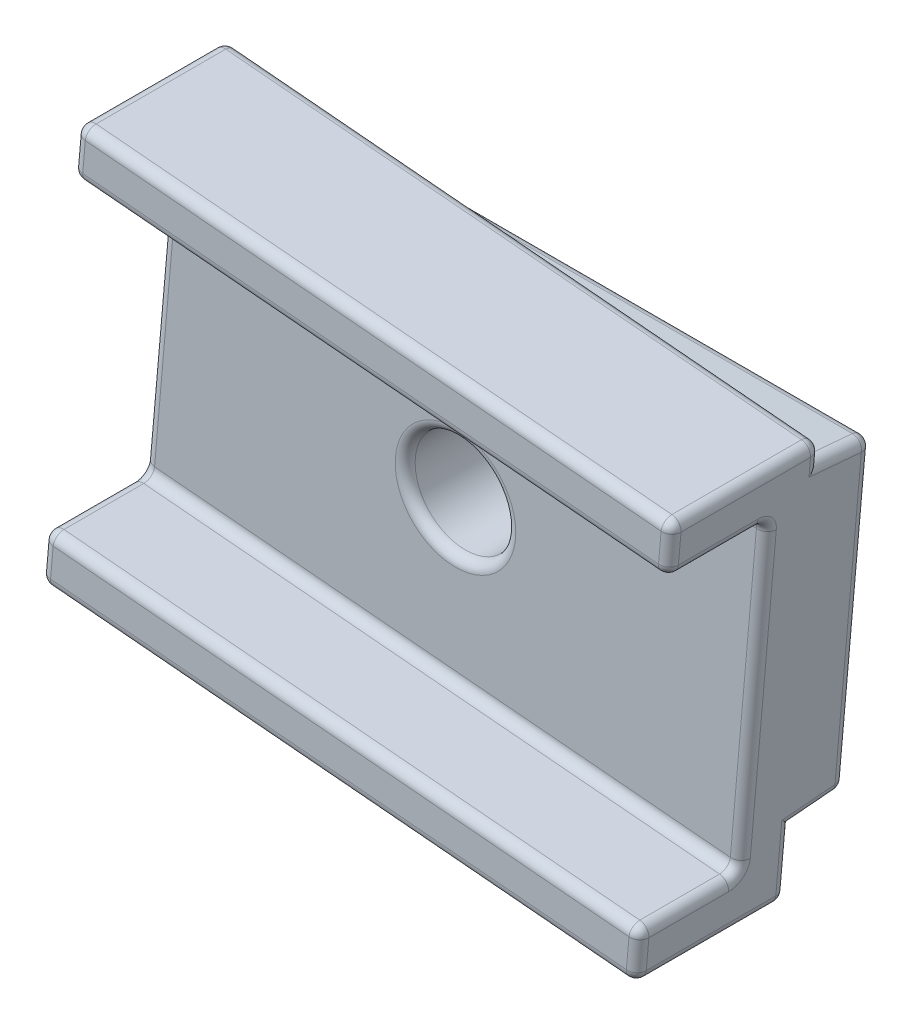
SolidWorks part; units mm, degrees
ref_plane "Front Plane" through (0, 0, 0) normal (0, 0, 1) x (1, 0, 0)
ref_plane "Top Plane" through (0, 0, 0) normal (0, 1, 0) x (1, 0, 0)
ref_plane "Right Plane" through (0, 0, 0) normal (1, 0, 0) x (0, 0, -1)
sketch "Sketch1" plane through (0, 0, 0) normal (0, 0, 1) x (1, 0, 0)
  line L1 (0, 0) -> (60, 0)
  line L2 (0, 0) -> (0, 32)
  line L3 (0, 32) -> (60, 32)
  line L4 (60, 0) -> (60, 32)
  dimension "D1" = 32
  dimension "D2" = 60
extrude "Boss-Extrude1" add sketch "Sketch1" along normal blind 5.3
sketch "Sketch3" plane through (0, 0, 0) normal (-1, 0, 0) x (0, 0, 1)
  line L0 (5.3, 32.5) -> (5.3, -0.5)
  line L1 (5.3, 32) -> (5.3, 0) construction
  line L2 (5.3, -0.5) -> (0, 0)
  line L3 (5.3, 32.5) -> (0, 32)
  line L8 (0, 32) -> (0, 0)
  line L9 (0, 0) -> (5.3, 0)
  line L10 (5.3, 0) -> (5.3, 32)
  line L11 (5.3, 32) -> (0, 32)
  line L13 (0, 0) -> (5.3, 0)
  line L14 (5.3, 0) -> (5.3, 32)
  line L15 (5.3, 32) -> (0, 32)
  point P4 (5.3, 16)
  line M7 (0, 0) -> (5.3, 0)
  line M9 (5.3, 32) -> (0, 32)
  dimension "D1" = 33
  dimension "D2" = 0
extrude "Boss-Extrude2" add sketch "Sketch3" against normal up to surface (60 mm away) contours L0 L3 M9 | L2 L0 M7 region at (0, 32.1667, 3.5333) region at (0, -0.1667, 3.5333) up to face at (60, 16, 2.65)
sketch "Sketch4" plane through (0, 0, 5.3) normal (0, 0, 1) x (1, 0, 0)
  line L0 (30, 32.5) -> (30, 16) construction
  line L1 (60, 32.5) -> (0, 32.5) construction
  line L2 (30, 16) -> (0, 16) construction
  line L3 (0, 32.5) -> (0, -0.5) construction
  line L4 (31.3945, 31.9391) -> (28.6055, 0.0609) construction
  line L5 (62.3171, -2.8885) -> (-5.1061, 3.0103)
  line L6 (62.3171, -2.8885) -> (65.1061, 28.9897)
  line L7 (65.1061, 28.9897) -> (-2.3171, 34.8885)
  line L8 (-5.1061, 3.0103) -> (-2.3171, 34.8885)
  line L9 (62.3171, -2.8885) -> (-2.3171, 34.8885) construction
  line L10 (65.1061, 28.9897) -> (-5.1061, 3.0103) construction
  line L11 (30, 16) -> (-3.7116, 18.9494) construction
  line L12 (1.5087, 34.5538) -> (-1.2803, 2.6756)
  line L13 (61.2803, 29.3244) -> (58.4913, -2.5538)
  line L14 (1.5087, 34.5538) -> (1.9444, 39.5348)
  line L15 (1.9444, 39.5348) -> (62.9835, 34.1945)
  line L16 (61.2803, 29.3244) -> (61.7161, 34.3054)
  line L17 (-1.2803, 2.6756) -> (-1.7161, -2.3054)
  line L18 (-1.7161, -2.3054) -> (58.0556, -7.5348)
  line L19 (58.4913, -2.5538) -> (58.0556, -7.5348)
  circle A0 centre (30, 16) radius 5.05
  line M3 (0, 32.5) -> (0, -0.5)
  line M4 (0, -0.5) -> (60, -0.5)
  line M5 (60, -0.5) -> (60, 32.5)
  line M6 (60, 32.5) -> (0, 32.5)
  dimension "D9" = 10.1
  dimension "D1" = 32
  dimension "D2" = 90
  dimension "D3" = 90
  dimension "D4" = 90
  dimension "D5" = 30
  dimension "D6" = 30
  dimension "D7" = 5
  dimension "D8" = 5
extrude "Boss-Extrude3" add sketch "Sketch4" along normal blind 5 contours L7 L12 M6 | L13 L7 L12 L5 A0 M5 M6 M3 M4 | L5 M4 M3 | L19 L5 L17 L18 M4 M3 | L13 L5 M4 | L13 L7 M5 | L7 M5 M6 | L7 L16 L15 L14 M6 M5 | L12 L5 M3 region at (32.0268, -3.072, 5.3) region at (50.7263, -1.1846, 5.3) region at (11.6722, 0.5212, 5.3) region at (17.5679, 1.7139, 5.3) region at (60.4268, 24.4837, 5.3) region at (27.9732, 35.072, 5.3) region at (-0.4268, 7.5163, 5.3) region at (48.3278, 31.4788, 5.3) region at (9.2737, 33.1846, 5.3)
extrude "Boss-Extrude4" add sketch "Sketch4<3>" along normal blind 15 contours L7 L16 L15 L14 M6 M5 | L7 M5 M6 | L19 L5 L17 L18 M4 M3 | L5 M4 M3 region at (32.0268, -3.072, 5.3) region at (11.6722, 0.5212, 5.3) region at (27.9732, 35.072, 5.3) region at (48.3278, 31.4788, 5.3)
sketch "Sketch4<3>" plane through (0, 0, 5.3) normal (0, 0, 1) x (1, 0, 0) same geometry as "Sketch4"
sketch "Sketch6" plane through (0, 0, 5.3) normal (0, 0, -1) x (-1, 0, 0)
  line L0 (0, 17.3098) -> (0, -0.5)
  line L1 (0, 17.3098) -> (0, -0.5) construction
  line L2 (0, 17.3098) -> (1.7161, -2.3054) construction
  line L3 (0, -0.5) -> (1.5582, -0.5)
  line L4 (1.5582, -0.5) -> (0, 17.3098)
  line L5 (-60, 14.6902) -> (-60, 32.5)
  line L6 (-60, 32.5) -> (-61.5582, 32.5)
  line L7 (-61.7161, 34.3054) -> (-60, 14.6902) construction
  line L8 (-61.5582, 32.5) -> (-60, 14.6902)
extrude "Boss-Extrude5" add sketch "Sketch6" along normal blind 5.3
sketch "Sketch5" plane through (0, 0, 5.3) normal (0, 0, 1) x (1, 0, 0)
  line L0 (58.671, -0.5) -> (60, -0.5)
  line L1 (60, -0.5) -> (60, 14.6902)
  line L2 (60, 14.6902) -> (58.671, -0.5)
  line L3 (1.329, 32.5) -> (0, 32.5)
  line L4 (0, 32.5) -> (0, 17.3098)
  line L5 (0, 17.3098) -> (1.329, 32.5)
extrude "Cut-Extrude1" cut sketch "Sketch5" against normal blind 10
sketch "Sketch7" plane through (0, 0, 0) normal (1, 0, 0) x (0, 0, -1)
  line L0 (0, -0.5) -> (0, 0)
  line L1 (0, 0) -> (-5.3, -0.5)
  line L2 (-5.3, -0.5) -> (0, -0.5)
extrude "Cut-Extrude2" cut sketch "Sketch7" against normal blind 5
sketch "Sketch8" plane through (60, 0, 0) normal (-1, 0, 0) x (0, 0, 1)
  line L0 (5.3, 32.5) -> (0, 32)
  line L1 (0, 32) -> (0, 32.5)
  line L2 (0, 32.5) -> (5.3, 32.5)
extrude "Cut-Extrude3" cut sketch "Sketch8" against normal blind 5
extrude "Cut-Extrude4" cut sketch "Sketch4<4>" against normal blind 15 contours A0
sketch "Sketch4<4>" plane through (0, 0, 5.3) normal (0, 0, 1) x (1, 0, 0) same geometry as "Sketch4"
fillet "Fillet1" radius 1 36 edges at (1.3071, 32.25, 2.65) (1.6367, 36.0174, 5.3) (1.9444, 39.5348, 12.8) (1.5087, 34.5538, 15.3) (-1.2803, 2.6756, 15.3) (-1.6371, -1.4027, 5.3) (-1.5363, -0.25, 2.65) (-0.1146, 16, 0) (28.6002, 0, 0) (31.3998, 32, 0) (24.95, 16, 0) (60.1146, 16, 0) (58.6929, -0.25, 2.65) (58.3633, -4.0174, 5.3) (58.4913, -2.5538, 15.3) (61.2803, 29.3244, 15.3) (61.7161, 34.3054, 12.8) (61.6371, 33.4027, 5.3) (61.5363, 32.25, 2.65) (-1.7161, -2.3054, 12.8) (58.0556, -7.5348, 12.8) (28.1697, -4.9201, 5.3) (58.2735, -5.0443, 20.3) (28.1697, -4.9201, 20.3) (-1.4982, 0.1851, 20.3) (28.6055, 0.0609, 20.3) (31.8303, 36.9201, 20.3) (61.4982, 31.8149, 20.3) (31.3945, 31.9391, 20.3) (1.7265, 37.0443, 20.3) (31.3945, 31.9391, 10.3) (59.8858, 13.3853, 10.3) (28.6055, 0.0609, 10.3) (0.1142, 18.6147, 10.3) (35.05, 16, 10.3) (31.8303, 36.9201, 5.3)
